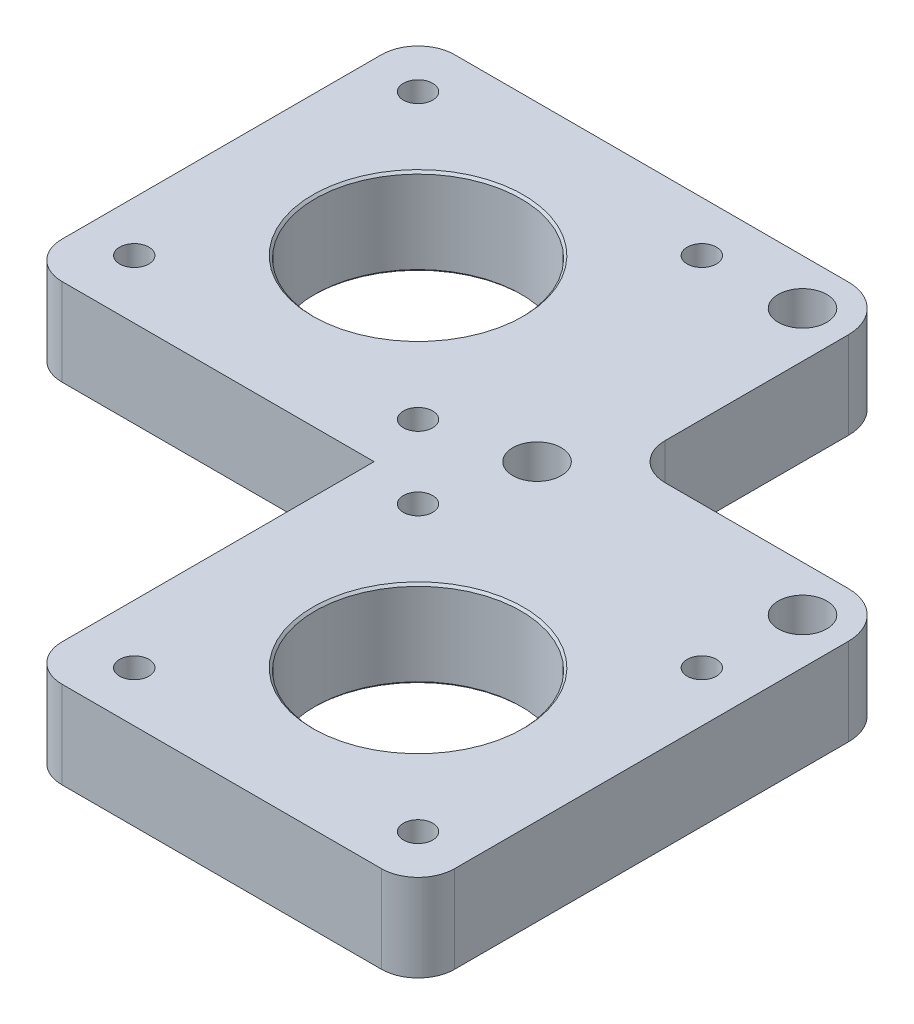
SolidWorks part; units mm, degrees
material "AISI 1045 Steel, cold drawn"
ref_plane "Front Plane" through (0, 0, 0) normal (0, 0, 1) x (1, 0, 0)
ref_plane "Top Plane" through (0, 0, 0) normal (0, 1, 0) x (1, 0, 0)
ref_plane "Right Plane" through (0, 0, 0) normal (1, 0, 0) x (0, 0, -1)
sketch "Sketch1" plane through (0, 0, 0) normal (0, 1, 0) x (1, 0, 0)
  line L1 (60, -21) -> (18, -21) construction
  line L2 (60, -21) -> (60, 21) construction
  line L3 (60, 21) -> (18, 21) construction
  line L4 (18, -21) -> (18, 21) construction
  line L5 (60, -21) -> (18, 21) construction
  line L6 (60, 21) -> (18, -21) construction
  line L7 (21, 18) -> (-21, 18) construction
  line L8 (21, 18) -> (21, 60) construction
  line L9 (21, 60) -> (-21, 60) construction
  line L10 (-21, 18) -> (-21, 60) construction
  line L11 (21, 18) -> (-21, 60) construction
  line L12 (21, 60) -> (-21, 18) construction
  line L14 (60, -21) -> (60, 31)
  line L15 (60, 31) -> (31, 31)
  line L16 (31, 31) -> (31, 60)
  line L17 (31, 60) -> (-21, 60)
  line L18 (-21, 60) -> (-21, 18)
  line L19 (-21, 18) -> (18, 18)
  line L20 (18, 18) -> (18, -21)
  line L21 (18, -21) -> (60, -21)
  point P0 (39, 0)
  point P5 (0, 39)
  dimension "D1" = 42
  dimension "D2" = 39
  dimension "D3" = 39
  dimension "D4" = 10
  dimension "D5" = 10
extrude "Boss-Extrude1" add sketch "Sketch1" along normal blind 9.525
hole_wizard "Ø22.5 (22.5) Diameter Hole1" positions "Sketch5" profile "Sketch7" hole size "Ø22.5" standard "ANSI Metric" end condition through all
sketch "Sketch5" plane through (0, 9.525, 0) normal (0, 1, 0) x (1, 0, 0)
  point P0 (0, 39)
  point P3 (39, 0)
sketch "Sketch7" plane through (0, 9.525, -39) normal (1, 0, 0) x (0, 0, 1)
  line L0 (0, 0) -> (0, 9.525)
  line L1 (0, 9.525) -> (11.25, 9.525)
  line L2 (11.25, 9.525) -> (11.25, 0)
  line L5 (11.25, 0) -> (0, 0)
  line L11 (0, -6.35) -> (0, 107.95) construction
  dimension "Thru Hole Dia." = 22.5
  dimension "Thru Hole Depth" = 9.525
sketch "Sketch8" plane through (0, 0, 0) normal (0, 1, 0) x (1, 0, 0)
  line L0 (21, 60) -> (-21, 18) construction
  line L1 (15.5, 23.5) -> (-15.5, 23.5)
  line L2 (15.5, 23.5) -> (15.5, 54.5)
  line L3 (15.5, 54.5) -> (-15.5, 54.5)
  line L4 (-15.5, 23.5) -> (-15.5, 54.5)
  line L5 (15.5, 23.5) -> (-15.5, 54.5) construction
  line L6 (15.5, 54.5) -> (-15.5, 23.5) construction
  line L7 (21, 18) -> (-21, 60) construction
  line L8 (60, 21) -> (18, -21) construction
  line L9 (23.5, -15.5) -> (54.5, -15.5)
  line L10 (23.5, -15.5) -> (23.5, 15.5)
  line L11 (23.5, 15.5) -> (54.5, 15.5)
  line L12 (54.5, -15.5) -> (54.5, 15.5)
  line L13 (23.5, -15.5) -> (54.5, 15.5) construction
  line L14 (23.5, 15.5) -> (54.5, -15.5) construction
  point P0 (0, 39)
  point P9 (39, 0)
  dimension "D1" = 31
hole_wizard "CBORE for M3 SHCS1" positions "Sketch9" profile "Sketch10" counterbore size "M3" standard "ANSI Metric" end condition through all
sketch "Sketch9" plane through (0, 0, 0) normal (0, -1, 0) x (-1, 0, 0)
  point P0 (-54.5, 15.5)
  point P3 (-23.5, 15.5)
  point P6 (-23.5, -15.5)
  point P9 (-54.5, -15.5)
  point P12 (-15.5, 54.5)
  point P15 (-15.5, 23.5)
  point P18 (15.5, 23.5)
  point P21 (15.5, 54.5)
sketch "Sketch10" plane through (54.5, 0, -15.5) normal (1, 0, 0) x (0, 0, -1)
  line L0 (0, 0) -> (0, 9.525)
  line L1 (0, 9.525) -> (1.6, 9.525)
  line L3 (1.6, 9.525) -> (1.6, 3)
  line L4 (1.6, 3) -> (3.25, 3)
  line L5 (3.25, 3) -> (3.25, 0)
  line L7 (3.25, 0) -> (0, 0)
  line L11 (0, -6.35) -> (0, 107.95) construction
  dimension "Thru Hole Dia." = 3.2
  dimension "Thru Hole Depth" = 9.525
  dimension "C'Bore Dia." = 6.5
  dimension "C'Bore Depth" = 3
hole_wizard "M5 Clearance Hole1" positions "Sketch11" profile "Sketch12" hole size "M5" standard "ANSI Metric" end condition through all
sketch "Sketch11" plane through (0, 9.525, 0) normal (0, 1, 0) x (1, 0, 0)
  line L0 (55, 26) -> (26, 26) construction
  line L1 (26, 26) -> (26, 55) construction
  line L3 (31, 31) -> (31, 60) construction
  line L4 (31, 60) -> (-21, 60) construction
  line L5 (60, -21) -> (60, 31) construction
  line L6 (60, 31) -> (31, 31) construction
  point P0 (26, 55)
  point P2 (26, 26)
  point P4 (55, 26)
  dimension "D1" = 5
  dimension "D2" = 5
  dimension "D3" = 5
  dimension "D4" = 5
sketch "Sketch12" plane through (26, 9.525, -55) normal (1, 0, 0) x (0, 0, 1)
  line L0 (0, 0) -> (0, 9.525)
  line L1 (0, 9.525) -> (2.65, 9.525)
  line L2 (2.65, 9.525) -> (2.65, 0)
  line L5 (2.65, 0) -> (0, 0)
  line L11 (0, -6.35) -> (0, 107.95) construction
  dimension "Thru Hole Dia." = 5.3
  dimension "Thru Hole Depth" = 9.525
hole_wizard "Tap Drill for M5x0.8 Tap1" positions "Sketch13" profile "Sketch15" hole size "M5x0.8" standard "ANSI Metric"
sketch "Sketch13" plane through (0, 0, -18) normal (0, 0, 1) x (1, 0, 0)
  line L3 (-21, 9.525) -> (-21, 0) construction
  point P0 (5, 4.7625)
  point P2 (-8.75, 4.7625)
  point P22 (-21, 4.7625)
  dimension "D1" = 8.75
  dimension "D2" = 5
sketch "Sketch15" plane through (5, 4.7625, -18) normal (1, 0, 0) x (0, -1, 0)
  line L0 (0, 0) -> (0, 9.2618)
  line L1 (0, 9.2618) -> (2.1, 8)
  line L2 (2.1, 8) -> (2.1, 0)
  line L5 (2.1, 0) -> (0, 0)
  line L10 (0, 9.2618) -> (-2.1, 8) construction
  line L11 (0, -6.35) -> (0, 107.95) construction
  dimension "Hole Dia." = 4.2
  dimension "Hole Depth" = 8
  dimension "Drill Angle" = 118
ref_plane "Plane1" through (0, 0, 0) normal (0.7071, 0, 0.7071) x (0.7071, 0, -0.7071)
mirror "Mirror1" about plane through (0, 0, 0) normal (0.7071, 0, 0.7071) of "Tap Drill for M5x0.8 Tap1"
sketch "Sketch16" plane through (0, 9.525, 0) normal (0, 1, 0) x (1, 0, 0)
  line L1 (17.1, 17.1) -> (-21, 17.1)
  line L2 (17.1, 17.1) -> (17.1, -21)
  line L6 (-21, 17.1) -> (-21, 18)
  line L7 (-21, 18) -> (18, 18)
  line L8 (18, 18) -> (18, -21)
  line L9 (18, -21) -> (17.1, -21)
  circle A0 centre (39, 0) radius 11.25 construction
  dimension "D1" = 21.9
extrude "Boss-Extrude2" add sketch "Sketch16" against normal up to surface (9.525 mm away) up to face at (26, 0, -52.35)
fillet "Fillet2" radius 4 5 edges at (-21, 4.7625, -60) (31, 4.7625, -31) (60, 4.7625, 21) (17.1, 4.7625, 21) (-21, 4.7625, -17.1)
fillet "Fillet3" radius 5 2 edges at (60, 4.7625, -31) (31, 4.7625, -60)
chamfer "Chamfer1" distance 0.25 angle 45 4 edges at (39, 9.525, 11.25) (39, 0, 11.25) (0, 9.525, -27.75) (0, 0, -27.75)
